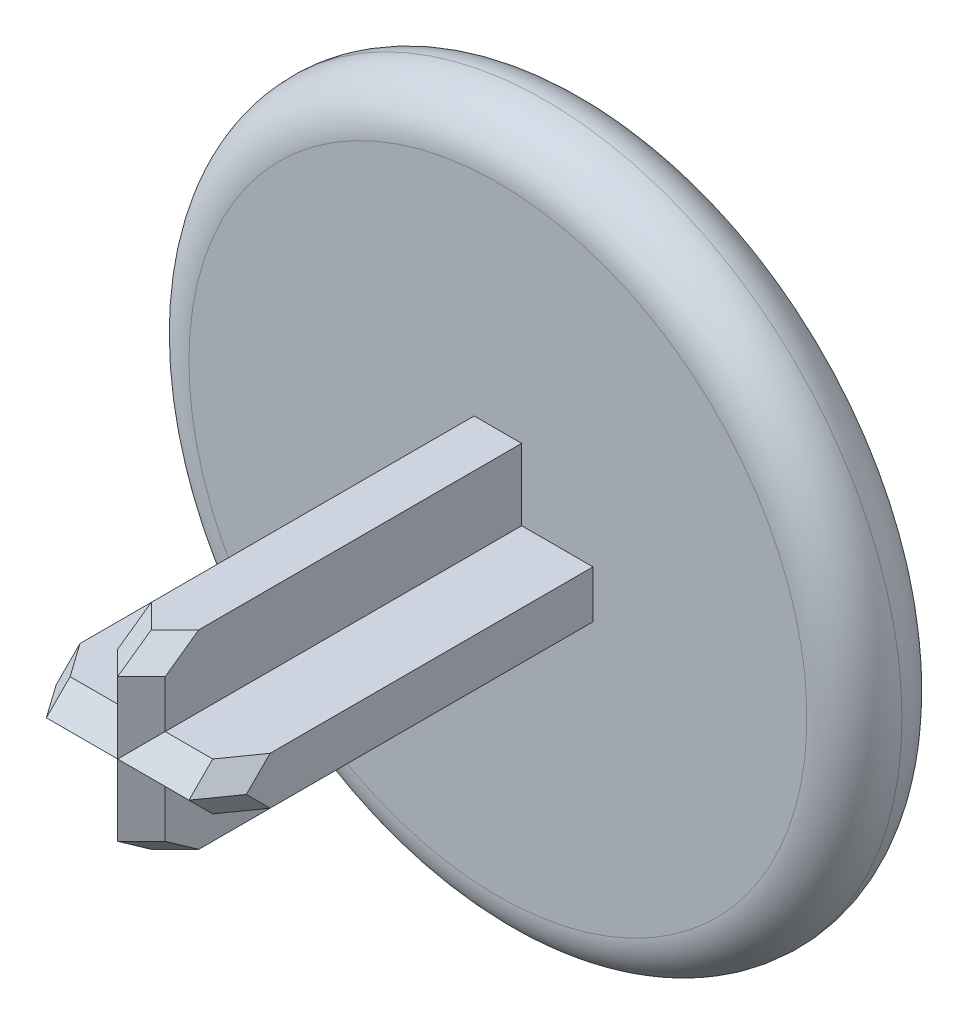
SolidWorks part; units mm, degrees
ref_plane "前视基准面" through (0, 0, 0) normal (0, 0, 1) x (1, 0, 0)
ref_plane "上视基准面" through (0, 0, 0) normal (0, 1, 0) x (1, 0, 0)
ref_plane "右视基准面" through (0, 0, 0) normal (1, 0, 0) x (0, 0, -1)
sketch "草图1" plane through (0, 0, 0) normal (0, 0, 1) x (1, 0, 0)
  line L1 (-2, 0.5) -> (2, 0.5)
  line L2 (-2, 0.5) -> (-2, -0.5)
  line L3 (-2, -0.5) -> (2, -0.5)
  line L4 (2, 0.5) -> (2, -0.5)
  line L5 (0, -0.5) -> (0, 0.5) construction
  line L6 (-2, 0) -> (2, 0) construction
  line L7 (-0.5, 2) -> (0.5, 2)
  line L8 (-0.5, 2) -> (-0.5, -2)
  line L9 (-0.5, -2) -> (0.5, -2)
  line L10 (0.5, 2) -> (0.5, -2)
  line L11 (0, -2) -> (0, 2) construction
  line L12 (-0.5, 0) -> (0.5, 0) construction
  point P0 (0, 0)
  point P4 (0, 0)
  dimension "D1" = 4
  dimension "D2" = 4
  dimension "D3" = 1
  dimension "D4" = 1
extrude "凸台-拉伸1" add sketch "草图1" along normal blind 8 contours L10 L7 L8 L1 | L10 L1 L8 L3 | L8 L1 L2 L3 | L1 L10 L3 L4 | L10 L9 L8 L7 region at (-1.25, 0, 0) region at (0, 1.25, 0) region at (0, 0, 0) region at (1.25, 0, 0)
chamfer "倒角1" distance 0.5 angle 45 8 edges at (-1.25, -0.5, 8) (-0.5, -1.25, 8) (0.5, -1.25, 8) (1.25, -0.5, 8) (-1.25, 0.5, 8) (-0.5, 1.25, 8) (1.25, 0.5, 8) (0.5, 1.25, 8) tangent propagation no
chamfer "倒角2" distance 0.5 angle 45 8 edges at (-2, -0.25, 7.75) (-2, 0.25, 7.75) (-0.25, -2, 7.75) (0.25, -2, 7.75) (2, -0.25, 7.75) (2, 0.25, 7.75) (-0.25, 2, 7.75) (0.25, 2, 7.75)
ref_plane "基准面1" through (0, 0, 0) normal (0, 0, -1) x (-1, 0, 0)
sketch "草图2" plane through (0, 0, 0) normal (0, 0, -1) x (-1, 0, 0)
  circle A0 centre (0, 0) radius 7.5
  dimension "D1" = 15
extrude "凸台-拉伸2" add sketch "草图2" along normal blind 2
fillet "圆角1" radius 1 2 edges at (-7.5, 0, 0) (-7.5, 0, -2)
